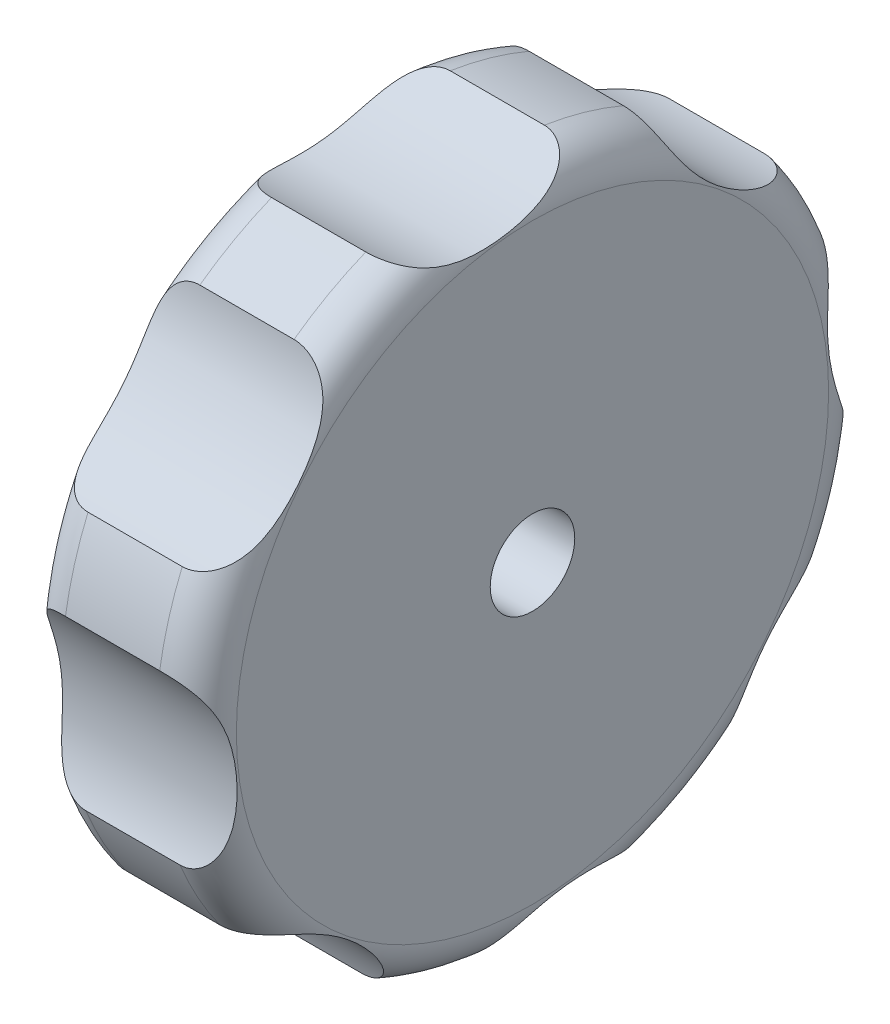
SolidWorks part; units mm, degrees
ref_plane "Front Plane" through (0, 0, 0) normal (0, 0, 1) x (1, 0, 0)
ref_plane "Top Plane" through (0, 0, 0) normal (0, 1, 0) x (1, 0, 0)
ref_plane "Right Plane" through (0, 0, 0) normal (1, 0, 0) x (0, 0, -1)
sketch "Sketch1" plane through (0, 0, 0) normal (1, 0, 0) x (0, 0, -1)
  circle A0 centre (0, 0) radius 3.14
  circle A1 centre (0, 0) radius 25
  dimension "D1" = 6.28
  dimension "D2" = 50
extrude "Boss-Extrude1" add sketch "Sketch1" along normal blind 13 contours A0 | A1 A0 region at (0, 0, 0) region at (0, 0, 24.2929)
extrude "Cut-Extrude1" cut sketch "Sketch1<3>" along normal up to next contours A0 region at (0, 0, 0)
sketch "Sketch1<3>" plane through (0, 0, 0) normal (1, 0, 0) x (0, 0, -1) same geometry as "Sketch1"
fillet "Fillet1" radius 3 1 edges at (13, 0, -25)
fillet "Fillet2" radius 3 1 edges at (0, 0, -25)
sketch "Sketch2" plane through (13, 0, 0) normal (1, 0, 0) x (0, 0, -1)
  circle A0 centre (-3.9541, 34.4317) radius 12.5
  dimension "D1" = 25
extrude "Cut-Extrude2" cut sketch "Sketch2" against normal up to next
ref_axis "Axis1" through (0, 0, 0) along (1, 0, 0)
pattern_circular "CirPattern1" count 8 over 360 about axis through (0, 0, 0) along (1, 0, 0) of face at (6.5, 23.0111, 2.6426)
sketch "Sketch3" plane through (0, 0, 0) normal (-1, 0, 0) x (0, 0, 1)
  line L1 (6.3624, 0) -> (3.1812, 5.51)
  line L2 (3.1812, 5.51) -> (-3.1812, 5.51)
  line L3 (-3.1812, 5.51) -> (-6.3624, 0)
  line L4 (-6.3624, 0) -> (-3.1812, -5.51)
  line L5 (-3.1812, -5.51) -> (3.1812, -5.51)
  line L6 (3.1812, -5.51) -> (6.3624, 0)
  circle A0 centre (0, 0) radius 5.51 construction
extrude "Cut-Extrude3" cut sketch "Sketch3" against normal blind 5.31
